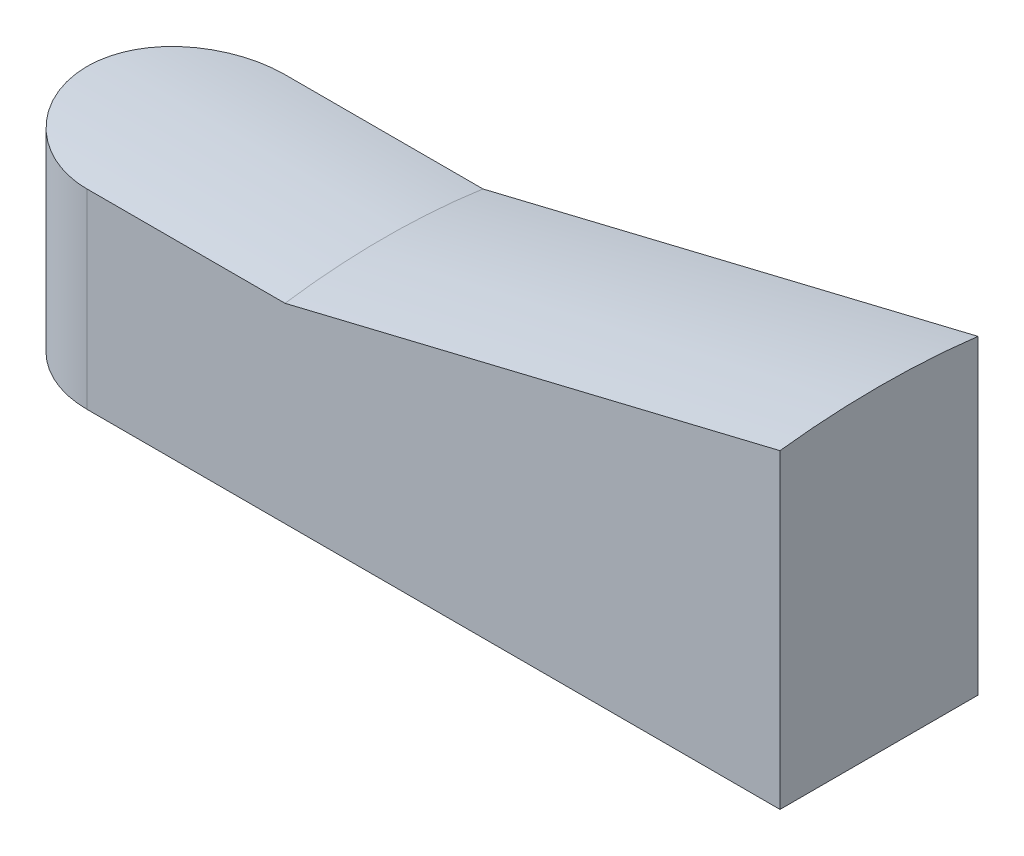
SolidWorks part; units mm, degrees
ref_plane "Front Plane" through (0, 0, 0) normal (0, 0, 1) x (1, 0, 0)
ref_plane "Top Plane" through (0, 0, 0) normal (0, 1, 0) x (1, 0, 0)
ref_plane "Right Plane" through (0, 0, 0) normal (1, 0, 0) x (0, 0, -1)
sketch "Sketch1" plane through (0, 0, 0) normal (0, 0, 1) x (1, 0, 0)
  line L0 (0, 0) -> (40, 0) construction
  line L1 (40, 0) -> (40, 41)
  line L2 (0, 35) -> (15, 35)
  line L3 (0, 35) -> (0, 0)
  line L4 (0, 0) -> (40, 0)
  line L5 (15, 35) -> (40, 41)
  dimension "D1" = 40
  dimension "D2" = 41
  dimension "D3" = 35
  dimension "D4" = 25
revolve "Revolve1" add sketch "Sketch1" angle 50 about L0
sketch "Sketch2" plane through (40, 0, 0) normal (1, 0, 0) x (0, 0, -1)
  line L0 (5, 55) -> (5, 25)
  line L1 (-5, 25) -> (5, 25)
  line L2 (-5, 55) -> (-52.6771, 31.8542)
  line L3 (-52.6771, 31.8542) -> (-43.1809, -35.5055)
  line L4 (-43.1809, -35.5055) -> (23.4821, -41.6981)
  line L5 (23.4821, -41.6981) -> (44.6358, -16.5393)
  line L6 (-5, 25) -> (-5, 55)
  line L7 (44.6358, -16.5393) -> (46.4887, -14.3355)
  line L8 (5, 55) -> (49.4537, 39.5348)
  line L9 (49.4537, 39.5348) -> (46.4887, -14.3355)
  arc A1 (31.4078, 26.3543) -> (-31.4078, 26.3543) centre (0, 0) ccw construction
  dimension "D1" = 55
  dimension "D2" = 10
  dimension "D3" = 5
  dimension "D4" = 30
extrude "Cut-Extrude1" cut sketch "Sketch2" against normal through all
fillet "Fillet1" radius 5 2 edges at (0, 29.8205, 5) (0, 29.8205, -5)
